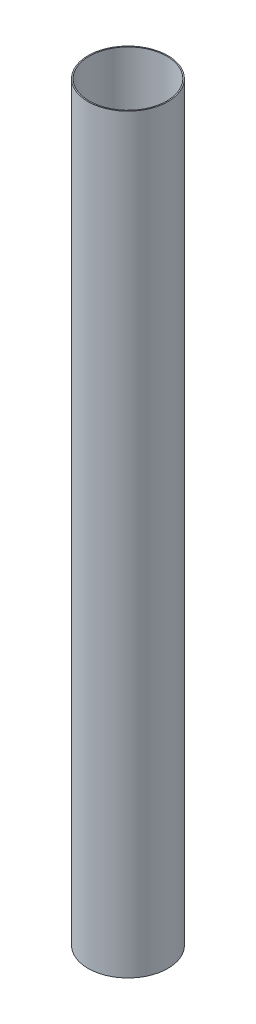
SolidWorks part; units mm, degrees
material "E-Glass Fiber"
ref_plane "Front Plane" through (0, 0, 0) normal (0, 0, 1) x (1, 0, 0)
ref_plane "Top Plane" through (0, 0, 0) normal (0, 1, 0) x (1, 0, 0)
ref_plane "Right Plane" through (0, 0, 0) normal (1, 0, 0) x (0, 0, -1)
sketch "Body Tube Profile" plane through (0, 0, 0) normal (0, 1, 0) x (1, 0, 0)
  circle A0 centre (0, 0) radius 76.2
  circle A1 centre (0, 0) radius 78.359
  dimension "D1" = 152.4
  dimension "D2" = 156.718
extrude "Body Tube Extrustion" [suppressed] add sketch "Body Tube Profile" along normal blind 1219.2
extrude "Boss-Extrude1" add sketch "Body Tube Profile<2>" along normal blind 1473.2
sketch "Body Tube Profile<2>" plane through (0, 0, 0) normal (0, 1, 0) x (1, 0, 0) same geometry as "Body Tube Profile"
equation "\"Length\" = 48"
equation "\"Outer Diameter\"= 6.17"
equation "\"Inner Diameter\"= 6"
equation "\"Wall Thickness\"= 0.085"
equation "\"D1@Body Tube Profile\" = \"Inner Diameter\""
equation "\"D2@Body Tube Profile\" = \"Outer Diameter\""
equation "\"D1@Body Tube Extrustion\" = \"Length\""
